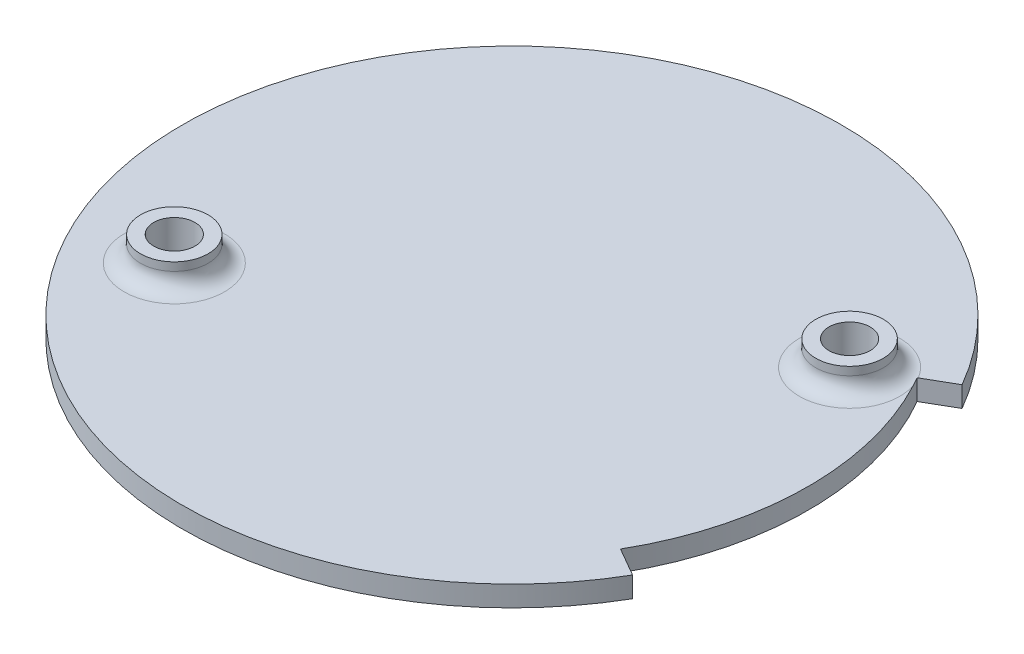
SolidWorks part; units mm, degrees
ref_plane "Front Plane" through (0, 0, 0) normal (0, 0, 1) x (1, 0, 0)
ref_plane "Top Plane" through (0, 0, 0) normal (0, 1, 0) x (1, 0, 0)
ref_plane "Right Plane" through (0, 0, 0) normal (1, 0, 0) x (0, 0, -1)
sketch "Sketch1" plane through (0, 0, 0) normal (0, 1, 0) x (1, 0, 0)
  line L0 (-13.1445, 33.02) -> (13.1445, 33.02) construction
  line L1 (0, 0) -> (0, 33.02) construction
  line L2 (13.1445, 33.02) -> (13.1445, 39.116) construction
  line L3 (13.1445, 39.116) -> (26.4795, 39.116) construction
  line L4 (0, 33.02) -> (0, 50.8) construction
  circle A0 centre (0, 0) radius 50.8
  circle A2 centre (-13.1445, 33.02) radius 1.905
  circle A3 centre (13.1445, 33.02) radius 1.905
  circle A4 centre (0, 0) radius 48.8
  dimension "D1" = 101.6
  dimension "D2" = 3.81
  dimension "D7" = 6.096
  dimension "D8" = 13.335
  dimension "D3" = 17.78
  dimension "D5" = 3.81
  dimension "D4" = 26.289
  dimension "D6" = 2
extrude "Boss-Extrude1" add sketch "Sketch1" along normal blind 3.175 contours A4 A2 A3 | A0 A4
sketch "Sketch3" plane through (0, 3.175, 0) normal (0, 1, 0) x (1, 0, 0)
  circle A0 centre (0, 0) radius 48.8
  circle A1 centre (0, 0) radius 50.8
  circle A2 centre (0, 0) radius 50.8
  dimension "D1" = 0
  dimension "D2" = 2
extrude "Boss-Extrude3" add sketch "Sketch3" along normal blind 12.7
sketch "Sketch4" plane through (0, 3.175, 0) normal (0, 1, 0) x (1, 0, 0)
  line L0 (0, 0) -> (25.4, 0) construction
  line L1 (25.4, 0) -> (25.4, -41.6687)
  line L2 (0, 0) -> (-25.4, 0) construction
  line L3 (-25.4, 0) -> (-25.4, -41.6687)
  line L4 (0, 0) -> (0, -45.72) construction
  arc A0 (-25.4, -38.0152) -> (25.4, -38.0152) centre (0, 0) ccw
  circle A2 centre (0, 0) radius 48.8 construction
  circle A3 centre (0, 0) radius 48.8 construction
  spline S0 degree 2 poles (-25.4, -20.8343) (0, -32.2542) (25.4, -20.8343) knots 0 0 0 1 1 1
  dimension "D1" = 45.72
  dimension "D3" = 25.4
  dimension "D4" = 25.4
extrude "Cut-Extrude1" cut sketch "Sketch4" against normal through all
fillet "Fillet2" radius 6.35 4 edges at (25.4, 1.5875, 20.8343) (-25.4, 1.5875, 20.8343) (-25.4, 1.5875, 38.0152) (25.4, 1.5875, 38.0152)
sketch "Sketch5" plane through (0, 3.175, 0) normal (0, 1, 0) x (1, 0, 0)
  line L0 (-13.1445, 37.925) -> (13.1445, 37.925)
  line L1 (-18.0495, 33.02) -> (-18.0495, -23.7298)
  line L2 (18.0495, 33.02) -> (18.0495, -23.7298)
  line L3 (-13.1445, 28.115) -> (13.1445, 28.115)
  line L4 (-8.2395, 33.02) -> (-8.2395, -25.9434)
  line L5 (8.2395, 33.02) -> (8.2395, -25.9434)
  line L6 (-8.2395, 3.5383) -> (8.2395, 3.5383)
  line L7 (-8.2395, -2.4617) -> (8.2395, -2.4617)
  circle A0 centre (13.1445, 33.02) radius 1.905 construction
  circle A1 centre (-13.1445, 33.02) radius 1.905 construction
  circle A2 centre (13.1445, 33.02) radius 1.905
  circle A3 centre (-13.1445, 33.02) radius 1.905
  circle A4 centre (-13.1445, 33.02) radius 4.905
  circle A5 centre (13.1445, 33.02) radius 4.905
  arc A6 (-17.2005, -23.9258) -> (-25.4, -30.0005) centre (-19.05, -30.0005) ccw construction
  arc A7 (25.4, -30.0005) -> (17.2005, -23.9258) centre (19.05, -30.0005) ccw construction
  parabola Q0 (-17.2005, -23.9258) -> (17.2005, -23.9258) focus (0, 1.7029) apex (0, -26.5443) construction
  parabola Q1 (-17.2005, -23.9258) -> (17.2005, -23.9258) focus (0, 1.7029) apex (0, -26.5443) construction
  circle M5 centre (13.1445, 33.02) radius 1.905
  circle M6 centre (-13.1445, 33.02) radius 1.905
  arc M9 (-25.4, -30.0005) -> (-17.2005, -23.9258) centre (-19.05, -30.0005) cw
  spline M10 degree 2 poles (-25.4, -20.8343) (0, -32.2542) (25.4, -20.8343) knots 0 0 0 1 1 1 only from (-17.2005, -23.9258) to (17.2005, -23.9258)
  arc M11 (17.2005, -23.9258) -> (25.4, -30.0005) centre (19.05, -30.0005) cw
  dimension "D2" = 6
  dimension "D1" = 3
extrude "Boss-Extrude4" add sketch "Sketch5" along normal blind 1 contours A5 L3 L5 L2 M10 M11 | L4 L7 L5 L6 | A4 L1 L4 L3 M9 M10 | A5 M5 | A5 L5 L3 | A5 L0 A4 L4 L3 L5 | A4 L3 L4 | A4 M6
sketch "Sketch6" plane through (0, 15.875, 0) normal (0, 1, 0) x (1, 0, 0)
  line L0 (0, 0) -> (43.9941, 25.4)
  line L1 (0, 0) -> (43.9941, -25.4)
  line L2 (0, 0) -> (50.8, 0) construction
  circle A0 centre (0, 0) radius 50.8 construction
  circle A1 centre (0, 0) radius 45.72
  circle A2 centre (0, 0) radius 50.8
  circle M4 centre (0, 0) radius 50.8
  circle M5 centre (0, 0) radius 48.8
  dimension "D1" = 101.6
  dimension "D2" = 91.44
  dimension "D3" = 30
  dimension "D4" = 30
extrude "Cut-Extrude2" cut sketch "Sketch6" against normal through all contours A1 L2 L0 M5 | L2 A1 L1 M5 | L2 L1 M5 M4 | L2 A2 L0 M5
sketch "Sketch7" plane through (0, 3.175, 0) normal (0, 1, 0) x (1, 0, 0)
  line L0 (39.5947, -22.86) -> (42.262, -24.4) construction
  line L1 (39.5947, 22.86) -> (42.262, 24.4) construction
  line L2 (39.5947, -22.86) -> (42.262, -24.4)
  line L3 (39.5947, 22.86) -> (42.262, 24.4)
  line L4 (36.823, -23.5692) -> (41.262, -26.1321)
  line L5 (36.823, 23.5692) -> (41.262, 26.1321)
  line L8 (42.262, -24.4) -> (39.5947, -22.86)
  line L9 (39.5947, 22.86) -> (42.262, 24.4)
  line L10 (42.262, -24.4) -> (39.5947, -22.86)
  line L11 (39.5947, 22.86) -> (42.262, 24.4)
  arc A0 (39.5947, -22.86) -> (39.5947, 22.86) centre (0, 0) ccw construction
  arc A1 (39.5947, -22.86) -> (39.5947, 22.86) centre (0, 0) ccw
  arc A2 (36.823, -23.5692) -> (36.823, 23.5692) centre (0, 0) ccw
  arc A5 (39.5947, -22.86) -> (39.5947, 22.86) centre (0, 0) ccw
  arc A6 (42.262, 24.4) -> (42.262, -24.4) centre (0, 0) ccw
  arc A7 (39.5947, -22.86) -> (39.5947, 22.86) centre (0, 0) ccw
  arc A8 (42.262, 24.4) -> (42.262, -24.4) centre (0, 0) ccw
  line M7 (42.262, -24.4) -> (39.5947, -22.86)
  arc M8 (39.5947, -22.86) -> (39.5947, 22.86) centre (0, 0) ccw
  line M9 (39.5947, 22.86) -> (42.262, 24.4)
  arc M10 (42.262, 24.4) -> (42.262, -24.4) centre (0, 0) ccw
  dimension "D1" = 2
  dimension "D2" = 0
extrude "Boss-Extrude5" add sketch "Sketch7" along normal up to surface (12.7 mm away) contours A2 L4 L5 M10 M7 M8 M9 up to face at (-3.336, 15.875, 0)
sketch "Sketch10" plane through (0, 3.175, 0) normal (0, 1, 0) x (1, 0, 0)
  line L0 (-32.9956, -19.05) -> (32.9956, 19.05) construction
  line L1 (0, 0) -> (0, 37.925) construction
  line L2 (-13.1445, 37.925) -> (13.1445, 37.925) construction
  circle A0 centre (-32.9956, -19.05) radius 1.5
  circle A1 centre (32.9956, 19.05) radius 1.5
  dimension "D1" = 3
  dimension "D2" = 3
  dimension "D3" = 76.2
  dimension "D4" = 60
extrude "Cut-Extrude4" cut sketch "Sketch10" against normal through all
sketch "Sketch11" plane through (0, 3.175, 0) normal (0, 1, 0) x (1, 0, 0)
  line L0 (32.9956, 23.09) -> (37.1253, 23.09)
  line L1 (32.9956, 15.01) -> (43.1859, 15.01)
  circle A0 centre (32.9956, 19.05) radius 1.5 construction
  circle A1 centre (-32.9956, -19.05) radius 1.5 construction
  circle A2 centre (32.9956, 19.05) radius 1.5
  circle A3 centre (-32.9956, -19.05) radius 1.5
  circle A4 centre (-32.9956, -19.05) radius 4.04
  circle A5 centre (32.9956, 19.05) radius 4.04
  arc A6 (36.823, -23.5692) -> (36.823, 23.5692) centre (0, 0) ccw construction
  arc A7 (39.5947, -22.86) -> (39.5947, 22.86) centre (0, 0) ccw construction
  arc A8 (36.823, -23.5692) -> (36.823, 23.5692) centre (0, 0) ccw construction
  arc A9 (36.823, -23.5692) -> (36.823, 23.5692) centre (0, 0) ccw
  circle M1 centre (-32.9956, -19.05) radius 1.5
  circle M2 centre (32.9956, 19.05) radius 1.5
  arc M18 (36.823, -23.5692) -> (36.823, 23.5692) centre (0, 0) ccw
  dimension "D1" = 2.54
extrude "Boss-Extrude7" add sketch "Sketch11" along normal up to surface (12.7 mm away) contours A5 L1 L0 M18 | A5 M2 | A4 M1
sketch "Sketch12" plane through (0, 0, 0) normal (0, -1, 0) x (1, 0, 0)
  line L0 (0, 0) -> (35.921, 35.921) construction
  line L1 (0, 0) -> (35.921, -35.921) construction
  line L2 (0, 0) -> (0, 26.5443) construction
  line L3 (0, 0) -> (-35.921, -35.921) construction
  line L4 (0, 0) -> (-35.921, 35.921) construction
  line L7 (39.5947, 22.86) -> (43.9941, 25.4)
  line L8 (43.9941, -25.4) -> (39.5947, -22.86)
  line L9 (39.5947, 22.86) -> (43.9941, 25.4)
  line L10 (43.9941, -25.4) -> (39.5947, -22.86)
  arc A0 (43.9941, 25.4) -> (43.9941, -25.4) centre (0, 0) ccw construction
  circle A1 centre (35.921, 35.921) radius 9.525
  circle A2 centre (35.921, -35.921) radius 9.525
  circle A3 centre (-35.921, -35.921) radius 9.525
  circle A4 centre (-35.921, 35.921) radius 9.525
  arc A7 (39.5947, -22.86) -> (39.5947, 22.86) centre (0, 0) ccw
  arc A8 (43.9941, 25.4) -> (43.9941, -25.4) centre (0, 0) ccw
  arc A9 (39.5947, -22.86) -> (39.5947, 22.86) centre (0, 0) ccw
  arc A10 (43.9941, 25.4) -> (43.9941, -25.4) centre (0, 0) ccw
  parabola Q0 (-17.2005, 23.9258) -> (17.2005, 23.9258) focus (0, -1.7029) apex (0, 26.5443) construction
  parabola Q1 (-8.2395, 25.9434) -> (8.2395, 25.9434) focus (0, -1.7029) apex (0, 26.5443) construction
  arc M14 (43.9941, 25.4) -> (43.9941, -25.4) centre (0, 0) ccw
  dimension "D5" = 19.05
  dimension "D6" = 19.05
  dimension "D7" = 19.05
  dimension "D8" = 19.05
  dimension "D1" = 45
  dimension "D2" = 90
  dimension "D3" = 90
  dimension "D4" = 90
  dimension "D9" = 0
extrude "Boss-Extrude8" add sketch "Sketch12" along normal blind 38.1 contours A1 M14 | A2 M14 | A4 M14 | A3 M14
fillet "Fillet4" radius 3.175 8 edges at (-41.9951, -19.05, -28.5841) (-28.5841, -19.05, -41.9951) (28.5841, -19.05, -41.9951) (41.9951, -19.05, -28.5841) (-28.5841, -19.05, 41.9951) (-41.9951, -19.05, 28.5841) (41.9951, -19.05, 28.5841) (28.5841, -19.05, 41.9951)
sketch "Sketch13" plane through (0, -38.1, 0) normal (0, -1, 0) x (1, 0, 0)
  line L0 (35.921, 35.921) -> (0, 0) construction
  line L1 (35.023, 35.023) -> (30.5329, 39.5131)
  line L2 (35.023, 35.023) -> (39.5131, 30.5329)
  line L3 (39.5131, 30.5329) -> (35.921, 26.9408)
  line L4 (35.921, 26.9408) -> (26.9408, 35.921)
  line L5 (26.9408, 35.921) -> (30.5329, 39.5131)
  line L6 (26.7417, -35.722) -> (35.722, -26.7417)
  line L7 (35.722, -26.7417) -> (39.3141, -30.3338)
  line L8 (34.8239, -34.8239) -> (39.3141, -30.3338)
  line L9 (34.8239, -34.8239) -> (30.3338, -39.3141)
  line L10 (30.3338, -39.3141) -> (26.7417, -35.722)
  line L11 (-35.921, -26.5427) -> (-26.9408, -35.5229)
  line L12 (-26.9408, -35.5229) -> (-30.5329, -39.115)
  line L13 (-35.023, -34.6249) -> (-30.5329, -39.115)
  line L14 (-35.023, -34.6249) -> (-39.5131, -30.1348)
  line L15 (-39.5131, -30.1348) -> (-35.921, -26.5427)
  line L16 (-26.7417, 36.1201) -> (-35.722, 27.1398)
  line L17 (-35.722, 27.1398) -> (-39.3141, 30.7319)
  line L18 (-34.8239, 35.2221) -> (-39.3141, 30.7319)
  line L19 (-34.8239, 35.2221) -> (-30.3338, 39.7122)
  line L20 (-30.3338, 39.7122) -> (-26.7417, 36.1201)
  arc A0 (39.7063, 31.6867) -> (31.6867, 39.7063) centre (0, 0) ccw construction
  point P32 (0, 0.1991)
  dimension "D1" = 12.7
  dimension "D2" = 6.35
  dimension "D3" = 5.08
  dimension "D5" = 44.45
  dimension "D4" = 4
extrude "Boss-Extrude9" add sketch "Sketch13" along normal blind 15.24
sketch "Sketch14" plane through (0, 15.875, 0) normal (0, 1, 0) x (1, 0, 0)
  circle A0 centre (-32.9956, -19.05) radius 1.5 construction
  circle A1 centre (32.9956, 19.05) radius 1.5
  circle A2 centre (32.9956, 19.05) radius 1.5
  circle A3 centre (-32.9956, -19.05) radius 1.5
  line M2 (43.9941, -25.4) -> (39.5947, -22.86)
  arc M3 (39.5947, -22.86) -> (39.5947, 22.86) centre (0, 0) ccw
  line M4 (39.5947, 22.86) -> (43.9941, 25.4)
  arc M5 (43.9941, 25.4) -> (43.9941, -25.4) centre (0, 0) ccw
  line M6 (36.823, -23.5692) -> (41.2265, -26.1116)
  arc M7 (41.2265, -26.1116) -> (41.2265, 26.1116) centre (0, 0) cw
  line M8 (41.2265, 26.1116) -> (36.823, 23.5692)
  arc M9 (36.823, 23.5692) -> (37.1253, 23.09) centre (0, 0) cw
  line M10 (37.1253, 23.09) -> (32.9956, 23.09)
  arc M11 (32.9956, 23.09) -> (32.9956, 15.01) centre (32.9956, 19.05) ccw
  line M12 (32.9956, 15.01) -> (41.0626, 15.01)
  arc M13 (41.0626, 15.01) -> (36.823, -23.5692) centre (0, 0) cw
  circle M14 centre (32.9956, 19.05) radius 1.5
  dimension "D1" = 0
extrude "Boss-Extrude10" add sketch "Sketch14" along normal blind 3.175 contours A3 M6 M13 M12 M11 M10 M9 M8 M7 | M5 M2 M3 M4 M13 M6 M7 M8 M9 M10 M11 M12 M14
sketch "Sketch15" plane through (0, -53.34, 0) normal (0, -1, 0) x (1, 0, 0)
  line L0 (-90.5779, 69.2637) -> (77.8424, 62.3374)
  line L1 (-90.5779, 69.2637) -> (-95.9011, -60.1758)
  line L2 (77.8424, 62.3374) -> (72.5191, -67.1021)
  line L3 (-95.9011, -60.1758) -> (72.5191, -67.1021)
extrude "Cut-Extrude5" cut sketch "Sketch15" against normal up to surface (69.215 mm away) up to face at (26.341, 15.875, -9.463)
sketch "Sketch16" plane through (0, 19.05, 0) normal (0, 1, 0) x (1, 0, 0)
  circle A0 centre (-32.9956, -19.05) radius 3.175
  circle A1 centre (32.9956, 19.05) radius 3.175
  dimension "D1" = 6.35
  dimension "D2" = 6.35
extrude "Cut-Extrude6" cut sketch "Sketch16" against normal blind 1.27
sketch "Sketch17" plane through (0, 19.05, 0) normal (0, 1, 0) x (1, 0, 0)
  circle A13 centre (32.9956, 19.05) radius 3.175 construction
  circle A14 centre (32.9956, 19.05) radius 3.175
  circle A15 centre (-32.9956, -19.05) radius 3.175 construction
  circle A16 centre (-32.9956, -19.05) radius 3.175
  circle A17 centre (-32.9956, -19.05) radius 5.207
  circle A18 centre (32.9956, 19.05) radius 5.207
  circle A19 centre (-32.9956, -19.05) radius 1.143
  circle A20 centre (32.9956, 19.05) radius 1.143
  circle M2 centre (-32.9956, -19.05) radius 3.175
  circle M3 centre (32.9956, 19.05) radius 3.175
  dimension "D1" = 2.032
  dimension "D2" = 2.032
extrude "Boss-Extrude11" add sketch "Sketch17" along normal blind 3.81 contours A17 M2 | A18 M3
fillet "Fillet5" radius 2.54 2 edges at (32.9956, 19.05, -13.843) (-32.9956, 19.05, 24.257)
sketch "Sketch18" plane through (0, 15.875, 0) normal (0, -1, 0) x (1, 0, 0)
  circle A0 centre (-32.9956, 19.05) radius 1.65
  circle A1 centre (32.9956, -19.05) radius 1.65
  dimension "D1" = 3.3
  dimension "D2" = 3.3
extrude "Cut-Extrude7" cut sketch "Sketch18" against normal up to surface (1.905 mm away) up to face at (-32.9956, 17.78, 22.225)
